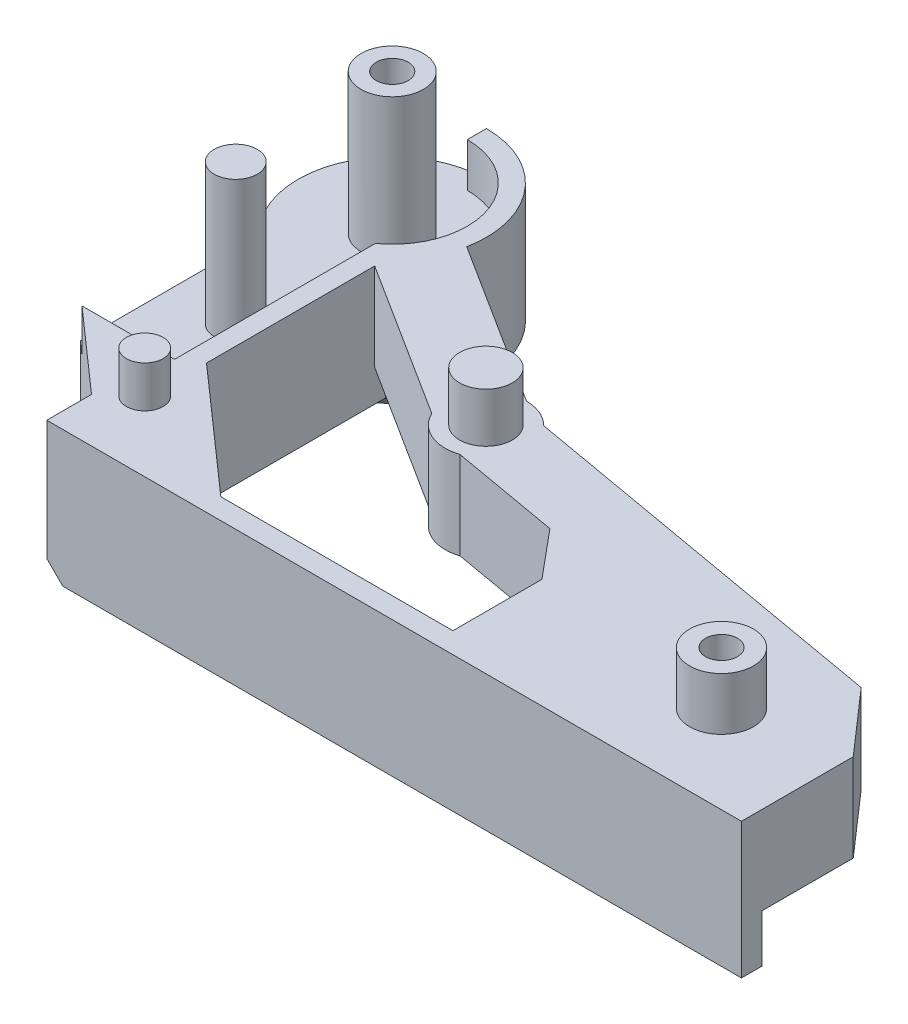
SolidWorks part; units mm, degrees
ref_plane "Front Plane" through (0, 0, 0) normal (0, 0, 1) x (1, 0, 0)
ref_plane "Top Plane" through (0, 0, 0) normal (0, 1, 0) x (1, 0, 0)
ref_plane "Right Plane" through (0, 0, 0) normal (1, 0, 0) x (0, 0, -1)
sketch "Sketch1" plane through (0, 0, 0) normal (0, 1, 0) x (1, 0, 0)
  line L0 (21.75, 0) -> (-21.75, 0)
  line L1 (-21.75, 0) -> (-21.75, 1.3)
  line L2 (-21.75, 1.3) -> (21.75, 1.3)
  line L3 (21.75, 1.3) -> (21.75, 0)
  line L4 (21.75, 0) -> (21.75, 7)
  line L5 (21.75, 7) -> (18.25, 11)
  line L6 (18.25, 11) -> (-7.25, 15.5)
  line L7 (-7.9973, 11.2654) -> (-0.119, 9.8751)
  line L8 (-7.25, 15.5) -> (-7.9973, 11.2654)
  line L9 (-0.119, 9.8751) -> (2.381, 6.8751)
  line L10 (2.381, 6.8751) -> (2.381, 1.3)
  line L11 (-8.9018, 11.6845) -> (-6.5982, 15.3155)
  line L12 (-6.5982, 15.3155) -> (-21.7974, 24.9583)
  line L13 (-21.7974, 24.9583) -> (-24.101, 21.3274)
  line L14 (-24.101, 21.3274) -> (-8.9018, 11.6845)
  line L15 (-7.75, 13.5) -> (-23.8, 23.6826) construction
  line L16 (-21.75, 0) -> (-21.75, 2.8)
  line L17 (-21.75, 2.8) -> (-27.75, 8.1)
  line L18 (-27.75, 8.1) -> (-27.75, 19.3)
  line L19 (-27.75, 19.3) -> (-19.85, 19.3)
  line L20 (-19.85, 19.3) -> (-19.85, 8.1)
  line L21 (-19.85, 8.1) -> (-12.1519, 1.3)
  circle A0 centre (-7.75, 13.5) radius 1.65
  circle A1 centre (-7.75, 13.5) radius 2.55
  circle A2 centre (-23.8, 23.6826) radius 5.9
  point P4 (0, 0)
  dimension "D15" = 3.3
  dimension "D16" = 5.1
  dimension "D25" = 11.8
  dimension "D1" = 1.3
  dimension "D2" = 43.5
  dimension "D3" = 0
  dimension "D4" = 7
  dimension "D5" = 4
  dimension "D6" = 3.5
  dimension "D7" = 29
  dimension "D8" = 15.5
  dimension "D9" = 4.3
  dimension "D10" = 8
  dimension "D11" = 3
  dimension "D12" = 2.5
  dimension "D13" = 29.5
  dimension "D14" = 13.5
  dimension "D17" = 4.3
  dimension "D18" = 18
  dimension "D19" = 2.8
  dimension "D20" = 6
  dimension "D21" = 5.3
  dimension "D22" = 11.2
  dimension "D23" = 7.9
  dimension "D24" = 11.2
extrude "Boss-Extrude1" add sketch "Sketch1" along normal blind 5.5 contours L15 A0 L8 L6 L12 A1 | A0 L11 L12 L6 L8 | L7 A1 L6 L12 L11 A0 L8 | L6 A1 L12 | A0 L15 A1 L14 L11 | L14 A1 L7 L8 A0 L11 | A1 L15 A2 L20 L14 | L14 A2 L19 | A2 L14 L20 | A2 L15 L13 L14 L19 | L15 A2 L12 L13 | L12 A2 L19 L14 L13 | L19 A2 L14 | A2 L18 L17 L16 L2 L21 L20 L14 | L3 L2 L1 L0 | A1 L7 L9 L10 L2 L4 L5 L6 | L15 A1 L12 A2 | A1 region at (0, 0, -0.65) region at (9.2958, 0, -7.5009) region at (-22.2491, 0, -9.6998) region at (-5.4314, 0, -14.4307) region at (-6.8016, 0, -15.6679) region at (-14.8223, 0, -16.6916) region at (-20.0026, 0, -18.9483) region at (-24.5154, 0, -24.6388) region at (-23.8866, 0, -18.6736) region at (-8.5807, 0, -11.5298) region at (-6.9861, 0, -15.2256) region at (-8.5029, 0, -15.3336) region at (-13.6776, 0, -18.5626) region at (-20.3518, 0, -19.1736) region at (-9.6514, 0, -13.2605) region at (-21.5296, 0, -21.0085) region at (-20.3708, 0, -22.7622)
sketch "Sketch2" plane through (0, 5.5, 0) normal (0, 1, 0) x (1, 0, 0)
  circle A0 centre (-7.75, 13.5) radius 1.65
  dimension "D1" = 3.3
extrude "Cut-Extrude1" cut sketch "Sketch2" against normal blind 5.5
sketch "Sketch3" plane through (0, 5.5, 0) normal (0, 1, 0) x (1, 0, 0)
  line L0 (-19.85, 8.1) -> (-19.85, 19.3)
  line L1 (-27.75, 8.1) -> (-27.75, 19.3)
  line L2 (-27.75, 8.1) -> (-21.75, 2.8)
  line L3 (-21.75, 2.8) -> (-21.75, 0)
  line L4 (-21.75, 0) -> (21.75, 0)
  line L5 (21.75, 0) -> (21.75, 1.3)
  line L6 (21.75, 0) -> (21.75, 7) construction
  line L7 (21.75, 1.3) -> (-12.1519, 1.3)
  line L8 (-12.1519, 1.3) -> (-19.85, 8.1)
  circle A0 centre (-23.8, 23.6826) radius 5.9
  line M8 (2.381, 1.3) -> (-12.1519, 1.3)
  line M9 (-12.1519, 1.3) -> (-19.85, 8.1)
  line M10 (-19.85, 8.1) -> (-19.85, 18.6304)
  arc M14 (-18.0088, 22.5547) -> (-27.75, 19.3) centre (-23.8, 23.6826) ccw
  line M15 (-27.75, 19.3) -> (-27.75, 8.1)
  line M16 (-27.75, 8.1) -> (-21.75, 2.8)
  line M17 (-21.75, 2.8) -> (-21.75, 0)
  line M18 (-21.75, 0) -> (21.75, 0)
  line M19 (21.75, 0) -> (21.75, 7)
  dimension "D1" = 11.8
extrude "Boss-Extrude2" add sketch "Sketch3" along normal blind 3 contours A0 M14 | A0 L7 L0 M15 M16 M17 M18 M19 M8 M9 M10 region at (-16.3527, 5.5, -4.3018) region at (-23.8, 5.5, -23.6826)
sketch "Sketch4" plane through (0, 0, 0) normal (0, -1, 0) x (1, 0, 0)
  line L0 (-23.8, -29.5826) -> (-23.8, -7.3)
  line L1 (-23.8, -7.3) -> (-26.8443, -7.3)
  line L2 (-21.75, -2.8) -> (-27.75, -8.1) construction
  line L3 (-26.8443, -7.3) -> (-27.75, -8.1)
  line L4 (-27.75, -8.1) -> (-27.75, -19.3)
  arc A0 (-27.75, -19.3) -> (-18.0088, -22.5547) centre (-23.8, -23.6826) ccw construction
  circle A1 centre (-23.8, -23.6826) radius 5.9
  line M18 (-21.75, -2.8) -> (-27.75, -8.1)
  line M19 (-27.75, -8.1) -> (-27.75, -19.3)
  arc M20 (-27.75, -19.3) -> (-18.0088, -22.5547) centre (-23.8, -23.6826) ccw
  dimension "D2" = 11.8
  dimension "D1" = 0.8
extrude "Cut-Extrude2" cut sketch "Sketch4" against normal offset from surface (2.75 mm away) 5.75 contours L0 A1 M20 | A1 L0 L1 M18 M19 region at (-26.304, 0, -23.6826) region at (-25.8054, 0, -12.8326) up to face at (-11.928, 8.5, -7.8314)
sketch "Sketch5" plane through (0, 0, 0) normal (0, -1, 0) x (1, 0, 0)
  line L0 (21.75, 0) -> (-21.75, 0) construction
  circle A0 centre (-23.8, -23.6826) radius 1.95
  circle A1 centre (-23.8, -13.8826) radius 1.35
  circle A2 centre (-20, -4.3826) radius 1.15
  circle A3 centre (15.0006, -5.5) radius 2
  dimension "D1" = 3.9
  dimension "D3" = 2.7
  dimension "D7" = 2.3
  dimension "D8" = 4
  dimension "D2" = 0
  dimension "D4" = 3.8
  dimension "D5" = 9.5
  dimension "D6" = 9.8
  dimension "D9" = 38.8006
  dimension "D10" = 5.5
extrude "Cut-Extrude3" cut sketch "Sketch5" against normal offset from surface (4.3 mm away) 1.2 up to face at (-1.7017, 5.5, -11.7406)
sketch "Sketch7" plane through (0, 4.3, 0) normal (0, -1, 0) x (1, 0, 0)
  circle A0 centre (-23.8, -13.8826) radius 1.35
  circle A1 centre (-23.8, -23.6826) radius 1.95
  dimension "D1" = 3.9
  dimension "D2" = 2.7
extrude "Cut-Extrude4" cut sketch "Sketch7" against normal offset from surface (3 mm away) 1.2 contours A1 | A0 region at (-23.8, 4.3, -23.6826) up to face at (-11.928, 8.5, -7.8314)
chamfer "Chamfer1" distance 1 angle 45 5 edges at (-21.75, 8.5, -1.4) (-24.75, 8.5, -5.45) (-27.75, 8.5, -13.7) (-19.85, 8.5, -13.7) (-23.8, 8.5, -29.5826)
sketch "Sketch8" plane through (0, 0, 0) normal (0, -1, 0) x (1, 0, 0)
  line L0 (-23.8, -7.3) -> (-21.05, -7.3)
  line L1 (-21.05, -7.3) -> (-21.05, -19.8711)
  line L2 (-19.85, -18.6304) -> (-19.85, -8.1) construction
  line L3 (-23.8, -7.3) -> (-23.8, -18.9826)
  circle A0 centre (-23.8, -23.6826) radius 4.7
  arc A1 (-23.8, -29.5826) -> (-18.0088, -22.5547) centre (-23.8, -23.6826) ccw construction
  line M13 (-23.8, -15.2326) -> (-23.8, -21.7326)
  arc M14 (-23.8, -21.7326) -> (-23.8, -25.6326) centre (-23.8, -23.6826) cw
  line M15 (-23.8, -25.6326) -> (-23.8, -29.5826)
  line M26 (-23.8, -7.3) -> (-23.8, -12.5326)
  arc M27 (-23.8, -12.5326) -> (-23.8, -15.2326) centre (-23.8, -13.8826) cw
  dimension "D1" = 1.2
  dimension "D2" = 1.2
extrude "Cut-Extrude5" cut sketch "Sketch8" against normal up to surface (2.75 mm away) contours A0 L1 L0 M26 M27 M13 | A0 M15 M13 M14 region at (-22.3304, 0, -13.2293) region at (-21.5626, 0, -23.6826) up to face at (-25.7752, 2.75, -16.4522)
mirror "Mirror1" about plane through (0, 0, 0) normal (0, 1, 0) of bodies 107
delete or keep bodies "-1" type delete bodies bodies 107
sketch "Sketch9" plane through (0, -7.3, 0) normal (0, 1, 0) x (1, 0, 0)
  circle A0 centre (-23.8, 23.6826) radius 1.95
  dimension "D1" = 3.9
extrude "Boss-Extrude3" add sketch "Sketch9" along normal offset from surface (13.35 mm away) 8.8 up to face at (-24.6399, -2.75, -17.4563) offset beyond the face yes
sketch "Sketch10" plane through (0, 6.05, 0) normal (0, 1, 0) x (1, 0, 0)
  circle A0 centre (-23.8, 23.6826) radius 1
  dimension "D1" = 2
extrude "Cut-Extrude6" cut sketch "Sketch10" against normal up to surface (8.8 mm away) up to face at (-24.6399, -2.75, -17.4563)
sketch "Sketch11" plane through (0, -7.3, 0) normal (0, 1, 0) x (1, 0, 0)
  circle A0 centre (-23.8, 13.8826) radius 1.35
  dimension "D1" = 2.7
extrude "Boss-Extrude4" add sketch "Sketch11" along normal offset from surface (13.35 mm away) 8.8 up to face at (-24.6399, -2.75, -17.4563) offset beyond the face yes
sketch "Sketch12" plane through (0, -4.3, 0) normal (0, 1, 0) x (1, 0, 0)
  circle A0 centre (-20, 4.3826) radius 1.15
  dimension "D1" = 2.3
extrude "Boss-Extrude5" add sketch "Sketch12" along normal offset from surface (6.9 mm away) 2.6 up to face at (-20, 0, -5.5326) offset beyond the face yes
sketch "Sketch13" plane through (0, -4.3, 0) normal (0, 1, 0) x (1, 0, 0)
  circle A0 centre (15.0006, 5.5) radius 2
  dimension "D1" = 4
extrude "Boss-Extrude6" add sketch "Sketch13" along normal offset from surface (7.6 mm away) 3.3 up to face at (-20, 0, -5.5326) offset beyond the face yes
sketch "Sketch14" plane through (0, 3.3, 0) normal (0, 1, 0) x (1, 0, 0)
  circle A0 centre (15.0006, 5.5) radius 1
  dimension "D1" = 2
extrude "Cut-Extrude7" cut sketch "Sketch14" against normal up to surface (3.3 mm away) up to face at (-20, 0, -5.5326)
sketch "Sketch15" plane through (0, 0, 0) normal (0, 1, 0) x (1, 0, 0)
  circle A0 centre (-7.75, 13.5) radius 1.65
  dimension "D1" = 3.3
extrude "Boss-Extrude7" add sketch "Sketch15" against normal blind 1.2 and the other way blind 3.1
sketch "Sketch16" plane through (0, -1.2, 0) normal (0, -1, 0) x (1, 0, 0)
  circle A0 centre (-7.75, -13.5) radius 1
  dimension "D1" = 2
extrude "Cut-Extrude8" cut sketch "Sketch16" against normal offset from surface (3.1 mm away) 1.2 up to face at (-7.75, 3.1, -11.85)
